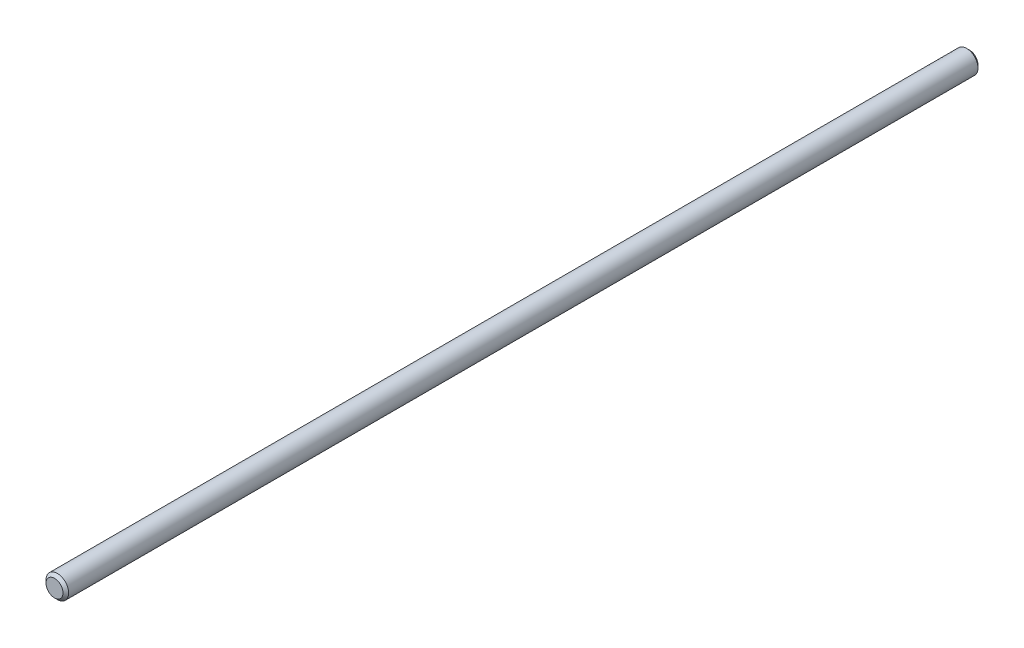
SolidWorks part; units mm, degrees
ref_plane "Front Plane" through (0, 0, 0) normal (0, 0, 1) x (1, 0, 0)
ref_plane "Top Plane" through (0, 0, 0) normal (0, 1, 0) x (1, 0, 0)
ref_plane "Right Plane" through (0, 0, 0) normal (1, 0, 0) x (0, 0, -1)
sketch "Sketch1" plane through (0, 0, 0) normal (0, 0, 1) x (1, 0, 0)
  circle A0 centre (0, 0) radius 4
  dimension "D1" = 8
extrude "Boss-Extrude1" add sketch "Sketch1" along normal blind 323
chamfer "Chamfer1" distance 1 angle 45 2 edges at (4, 0, 323) (4, 0, 0)
